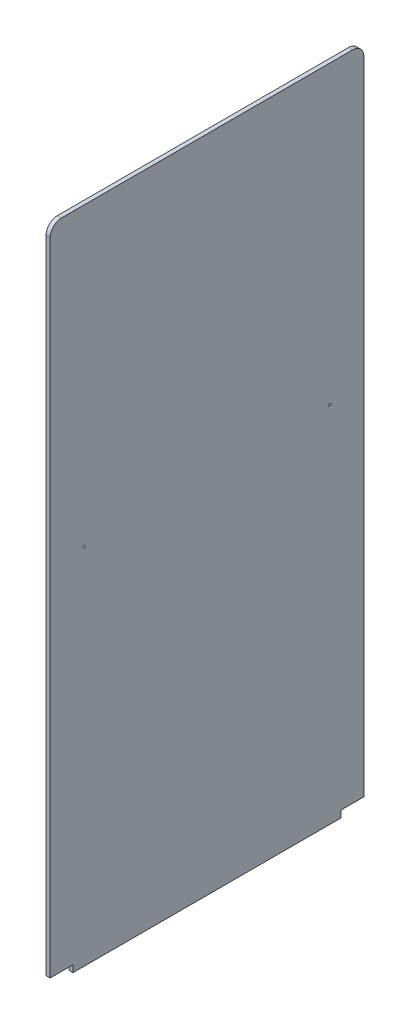
SolidWorks part; units mm, degrees
ref_plane "Front Plane" through (0, 0, 0) normal (0, 0, 1) x (1, 0, 0)
ref_plane "Top Plane" through (0, 0, 0) normal (0, 1, 0) x (1, 0, 0)
ref_plane "Right Plane" through (0, 0, 0) normal (1, 0, 0) x (0, 0, -1)
sketch "Sketch1" plane through (0, 0, 0) normal (1, 0, 0) x (0, 0, -1)
  line L1 (-69, -3) -> (69, -3)
  line L2 (-69, -3) -> (-69, 287)
  line L3 (-69, 287) -> (69, 287)
  line L4 (69, -3) -> (69, 287)
  point P4 (0, -3)
  dimension "D1" = 138
  dimension "D2" = 290
  dimension "D3" = 3
extrude "Boss-Extrude1" add sketch "Sketch1" along normal mid plane 1.8
sketch "Sketch2" plane through (0.9, 0, 0) normal (1, 0, 0) x (0, 0, -1)
  line L0 (0, 0) -> (0, -19.9753) construction
  line L1 (83.0391, 0) -> (59, 0)
  line L2 (83.0391, 0) -> (83.0391, -8.3383)
  line L3 (83.0391, -8.3383) -> (59, -8.3383)
  line L4 (59, 0) -> (59, -8.3383)
  line L5 (-59, 0) -> (-59, -8.3383)
  line L6 (-83.0391, -8.3383) -> (-59, -8.3383)
  line L7 (-83.0391, 0) -> (-83.0391, -8.3383)
  line L8 (-83.0391, 0) -> (-59, 0)
  dimension "D1" = 118
extrude "Cut-Extrude1" cut sketch "Sketch2" against normal blind 3
ref_axis "Axis1" through (0, 0, -91.3431) along (0, 0, 1)
sketch "Sketch3" plane through (0, 0, 69) normal (0, 0, 1) x (1, 0, 0)
  line L0 (0, 106.8391) -> (62.0206, 87.3854)
  line L1 (0, 106.8391) -> (64.4787, 115.0548)
  arc A0 (62.0206, 87.3854) -> (64.4787, 115.0548) centre (0, 106.8391) ccw
  point P0 (0, 106.8391)
  dimension "D1" = 65
sketch "Sketch4" plane through (0.9, 0, 0) normal (1, 0, 0) x (0, 0, -1)
  line L0 (-69, 156.8391) -> (90.793, 156.8391) construction
  line L1 (69, 0) -> (69, 287) construction
  line L2 (-69, 106.8391) -> (-69, 115.0548) construction
  line L3 (-76.4939, 106.8391) -> (-83.7925, 106.8391) construction
  circle A0 centre (-54, 156.8391) radius 0.5
  circle A1 centre (54, 156.8391) radius 0.5
  dimension "D1" = 1
  dimension "D2" = 15
  dimension "D3" = 15
  dimension "D4" = 50
extrude "Cut-Extrude2" cut sketch "Sketch4" against normal blind 10
fillet "Fillet1" radius 5 2 edges at (0, 287, -69) (0, 287, 69)
sketch "Sketch5" plane through (0.9, 0, 0) normal (1, 0, 0) x (0, 0, -1)
  line L0 (-54, 156.8391) -> (54, 156.8391)
  line L1 (-59, -3) -> (59, -3) construction
ref_axis "Axis2" through (0.9, 156.8391, 54) along (0, 0, -1)
sketch "Sketch6" plane through (0, 0, 69) normal (0, 0, 1) x (1, 0, 0)
  line L0 (0, 168.2036) -> (64.8764, 177.327)
ref_plane "Plane1" through (-0.9, 0, 0) normal (1, 0, 0) x (0, 0, -1)
sketch "Sketch7" plane through (-0.9, 0, 0) normal (-1, 0, 0) x (0, 0, 1)
  line L0 (-54, 156.8391) -> (54, 156.8391)
ref_axis "Axis3" through (-0.9, 156.8391, -54) along (0, 0, 1)
